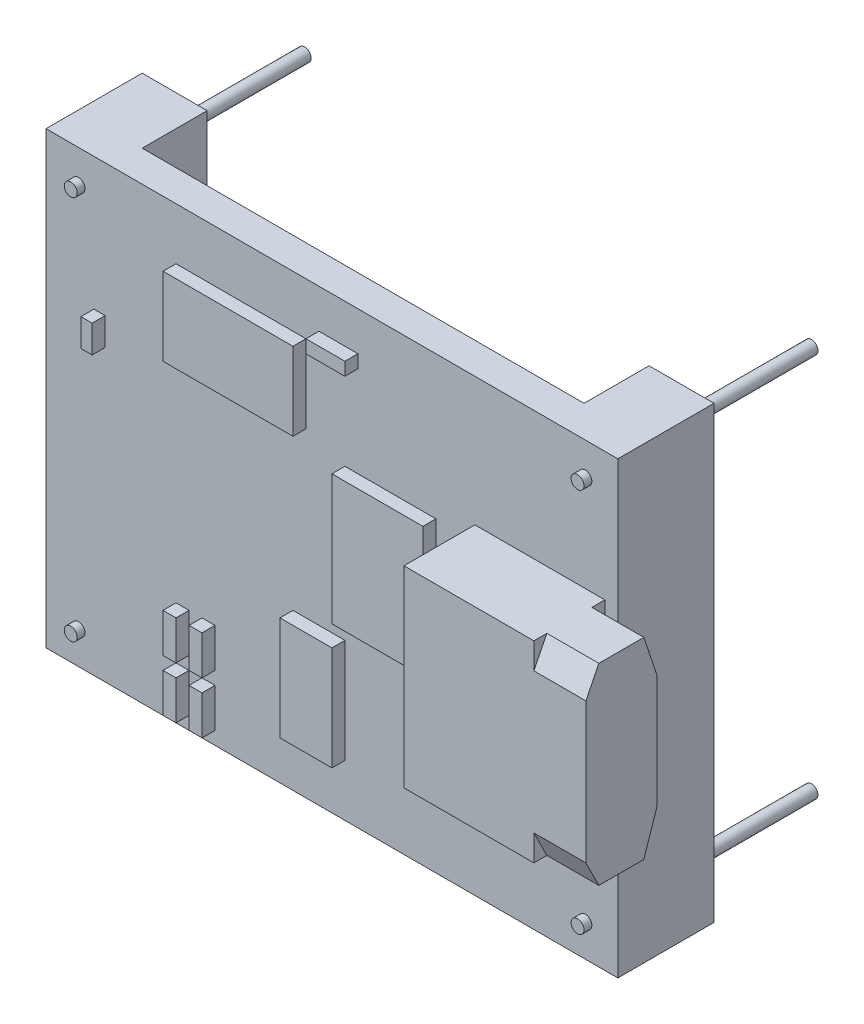
SolidWorks part; units mm, degrees
ref_plane "Plan de face" through (0, 0, 0) normal (0, 0, 1) x (1, 0, 0)
ref_plane "Plan de dessus" through (0, 0, 0) normal (0, 1, 0) x (1, 0, 0)
ref_plane "Plan de droite" through (0, 0, 0) normal (1, 0, 0) x (0, 0, -1)
sketch "Esquisse1" plane through (0, 0, 0) normal (0, 0, 1) x (1, 0, 0)
  line L1 (0, 0) -> (-22, 0)
  line L2 (0, 0) -> (0, 17.3)
  line L3 (0, 17.3) -> (-22, 17.3)
  line L4 (-22, 0) -> (-22, 17.3)
  dimension "D1" = 22
  dimension "D2" = 17.3
extrude "Boss.-Extru.1" add sketch "Esquisse1" along normal blind 1.2
sketch "Esquisse2" plane through (0, 0, 1.2) normal (0, 0, 1) x (1, 0, 0)
  line L0 (0, 0) -> (0, 17.3) construction
  line L1 (5.5, 4.95) -> (-5.5, 4.95)
  line L2 (5.5, 4.95) -> (5.5, 12.35)
  line L3 (5.5, 12.35) -> (-5.5, 12.35)
  line L4 (-5.5, 4.95) -> (-5.5, 12.35)
  line L5 (5.5, 4.95) -> (-5.5, 12.35) construction
  line L6 (5.5, 12.35) -> (-5.5, 4.95) construction
  line L7 (0, 12.35) -> (1.5, 12.35) construction
  line L8 (1.5, 12.35) -> (1.5, 4.95)
  point P0 (0, 8.65)
  line M5 (0, 0) -> (0, 17.3)
  dimension "D1" = 7.4
  dimension "D2" = 11
  dimension "D3" = 1.5
extrude "Boss.-Extru.2" add sketch "Esquisse2" along normal blind 2.73 contours L4 L1 L3 M5 | L8 L3 L1 M5 region at (0.75, 8.65, 1.2) region at (-2.75, 8.65, 1.2)
sketch "Esquisse3" plane through (0, 0, 0) normal (0, 0, -1) x (-1, 0, 0)
  line L0 (22, 0) -> (0, 0) construction
  line L1 (0, 17.3) -> (2.5, 17.3)
  line L2 (0, 17.3) -> (0, 0)
  line L3 (0, 0) -> (2.5, 0)
  line L4 (2.5, 17.3) -> (2.5, 0)
  line L5 (0, 17.3) -> (22, 17.3) construction
  line L6 (22, 0) -> (19.5, 0)
  line L7 (22, 0) -> (22, 17.3)
  line L8 (22, 17.3) -> (19.5, 17.3)
  line L9 (19.5, 0) -> (19.5, 17.3)
  dimension "D1" = 2.5
  dimension "D2" = 2.5
extrude "Boss.-Extru.3" add sketch "Esquisse3" along normal blind 2.5
sketch "Esquisse4" plane through (0, 0, -2.5) normal (0, 0, -1) x (-1, 0, 0)
  line L0 (2.5, 0) -> (2.5, 17.3) construction
  line L1 (0, 17.3) -> (2.5, 17.3)
  line L2 (0, 17.3) -> (0, 14.8)
  line L3 (0, 14.8) -> (2.5, 14.8)
  line L4 (2.5, 17.3) -> (2.5, 14.8)
  line L5 (2.5, 0) -> (2.5, 17.3) construction
  line L6 (0, 0) -> (2.5, 0)
  line L7 (0, 0) -> (0, 2.5)
  line L8 (0, 2.5) -> (2.5, 2.5)
  line L9 (2.5, 0) -> (2.5, 2.5)
  line L10 (22, 0) -> (22, 17.3) construction
  line L11 (19.5, 0) -> (22, 0)
  line L12 (19.5, 0) -> (19.5, 2.5)
  line L13 (19.5, 2.5) -> (22, 2.5)
  line L14 (22, 0) -> (22, 2.5)
  line L15 (19.5, 17.3) -> (19.5, 0) construction
  line L16 (22, 17.3) -> (19.5, 17.3)
  line L17 (22, 17.3) -> (22, 14.8)
  line L18 (22, 14.8) -> (19.5, 14.8)
  line L19 (19.5, 17.3) -> (19.5, 14.8)
  line L20 (0, 17.3) -> (2.5, 14.8) construction
  line L21 (19.5, 14.8) -> (22, 17.3) construction
  line L22 (22, 0) -> (19.5, 2.5) construction
  line L23 (2.5, 2.5) -> (0, 0) construction
  circle A0 centre (1.25, 1.25) radius 0.25
  circle A1 centre (1.25, 16.05) radius 0.25
  circle A2 centre (20.75, 16.05) radius 0.25
  circle A3 centre (20.75, 1.25) radius 0.25
  dimension "D5" = 0.5
  dimension "D6" = 0.5
  dimension "D7" = 0.5
  dimension "D8" = 0.5
  dimension "D1" = 2.5
  dimension "D2" = 2.5
  dimension "D3" = 2.5
  dimension "D4" = 2.5
extrude "Boss.-Extru.4" add sketch "Esquisse4" along normal blind 5 and the other way blind 4 contours A1 | A0 | A3 | A2
sketch "Esquisse5" plane through (0, 0, 1.2) normal (0, 0, 1) x (1, 0, 0)
  line L0 (-22, 0) -> (0, 0) construction
  line L1 (-10.5, 2) -> (-12.5, 2)
  line L2 (-10.5, 2) -> (-10.5, 6)
  line L3 (-10.5, 6) -> (-12.5, 6)
  line L4 (-12.5, 2) -> (-12.5, 6)
  line L5 (-15.5, 0.5) -> (-16, 0.5)
  line L6 (-15.5, 0.5) -> (-15.5, 2)
  line L7 (-15.5, 2) -> (-16, 2)
  line L8 (-16, 0.5) -> (-16, 2)
  line L9 (-16.5, 0.5) -> (-17, 0.5)
  line L10 (-16.5, 0.5) -> (-16.5, 2)
  line L11 (-16.5, 2) -> (-17, 2)
  line L12 (-17, 0.5) -> (-17, 2)
  line L13 (-15.5, 2.5) -> (-16, 2.5)
  line L14 (-15.5, 2.5) -> (-15.5, 4)
  line L15 (-15.5, 4) -> (-16, 4)
  line L16 (-16, 2.5) -> (-16, 4)
  line L17 (-16.5, 2.5) -> (-17, 2.5)
  line L18 (-16.5, 2.5) -> (-16.5, 4)
  line L19 (-16.5, 4) -> (-17, 4)
  line L20 (-17, 2.5) -> (-17, 4)
  line L21 (-12, 12.3) -> (-17, 12.3)
  line L22 (-12, 12.3) -> (-12, 15.3)
  line L23 (-12, 15.3) -> (-17, 15.3)
  line L24 (-17, 12.3) -> (-17, 15.3)
  line L25 (-10, 15.3) -> (-11.5, 15.3)
  line L26 (-10, 15.3) -> (-10, 15.8)
  line L27 (-10, 15.8) -> (-11.5, 15.8)
  line L28 (-11.5, 15.3) -> (-11.5, 15.8)
  line L33 (-19.7273, 11.1459) -> (-20.1614, 11.1459)
  line L34 (-19.7273, 11.1459) -> (-19.7273, 12.207)
  line L35 (-19.7273, 12.207) -> (-20.1614, 12.207)
  line L36 (-20.1614, 11.1459) -> (-20.1614, 12.207)
  line L37 (-22, 17.3) -> (-22, 0) construction
  line L38 (0, 17.3) -> (-22, 17.3) construction
  line L39 (-5.5, 4.95) -> (-5.5, 12.35) construction
  line L40 (-7, 6.8) -> (-10.5, 6.8)
  line L41 (-7, 6.8) -> (-7, 11.8)
  line L42 (-7, 11.8) -> (-10.5, 11.8)
  line L43 (-10.5, 6.8) -> (-10.5, 11.8)
  point P36 (-15.75, 2.5)
  point P37 (-16.75, 2.5)
  dimension "D1" = 2
  dimension "D2" = 4
  dimension "D3" = 1.5
  dimension "D4" = 1.5
  dimension "D5" = 1.5
  dimension "D6" = 1.5
  dimension "D7" = 0.5
  dimension "D8" = 0.5
  dimension "D9" = 0.5
  dimension "D10" = 0.5
  dimension "D11" = 0.5
  dimension "D12" = 0.5
  dimension "D13" = 0.5
  dimension "D14" = 0.5
  dimension "D15" = 0
  dimension "D16" = 0.5
  dimension "D17" = 5
  dimension "D18" = 3
  dimension "D19" = 2
  dimension "D20" = 5
  dimension "D21" = 3
  dimension "D22" = 2
  dimension "D23" = 5
  dimension "D26" = 1.5
  dimension "D27" = 0.5
  dimension "D28" = 1.5
  dimension "D29" = 12
  dimension "D31" = 3.5
  dimension "D32" = 5
  dimension "D33" = 1.5
  dimension "D34" = 5.5
extrude "Boss.-Extru.5" add sketch "Esquisse5" along normal blind 0.5
sketch "Esquisse8" plane through (1.5, 0, 0) normal (1, 0, 0) x (0, 0, -1)
  line L0 (-1.2, 4.95) -> (-1.2, 6.45) construction
  line L1 (-1.2, 4.95) -> (-1.2, 12.35) construction
  line L2 (-1.2, 6.45) -> (-1.2, 10.85) construction
  line L3 (-1.2, 12.35) -> (-1.2, 4.95) construction
  line L4 (-1.2, 10.85) -> (-1.2, 12.35) construction
  line L5 (-1.2, 6.45) -> (-1.2, 4.95)
  line L6 (-1.2, 4.95) -> (-1.7, 4.95)
  line L7 (-1.7, 2) -> (-1.7, 6) construction
  line L8 (-3.93, 4.95) -> (-1.2, 4.95) construction
  line L9 (-1.7, 4.95) -> (-1.2, 6.45)
  line L10 (-1.2, 10.85) -> (-1.7, 12.35)
  line L11 (-3.93, 12.35) -> (-1.2, 12.35) construction
  line L12 (-1.7, 12.3) -> (-1.7, 15.3) construction
  line L13 (-1.7, 12.35) -> (-1.2, 12.35)
  line L14 (-1.2, 12.35) -> (-1.2, 10.85)
  line L15 (-3.93, 4.95) -> (-3.93, 5.95) construction
  line L16 (-3.93, 12.35) -> (-3.93, 4.95) construction
  line L17 (-3.93, 5.95) -> (-3.93, 11.35) construction
  line L18 (-3.93, 11.35) -> (-3.93, 12.35) construction
  line L19 (-3.93, 12.35) -> (-3.43, 12.35) construction
  line L20 (-3.43, 12.35) -> (-3.43, 4.95) construction
  line L21 (-3.43, 4.95) -> (-3.93, 4.95) construction
  line L22 (-3.93, 4.95) -> (-3.93, 5.95)
  line L23 (-3.93, 5.95) -> (-3.43, 4.95)
  line L24 (-3.43, 4.95) -> (-3.93, 4.95)
  line L25 (-3.93, 11.35) -> (-3.43, 12.35)
  line L26 (-3.43, 12.35) -> (-3.93, 12.35)
  line L27 (-3.93, 12.35) -> (-3.93, 11.35)
  dimension "D1" = 1.5
  dimension "D2" = 1.5
  dimension "D3" = 1
  dimension "D4" = 0.5
  dimension "D5" = 1
extrude "Enlèv. mat.-Extru.4" cut sketch "Esquisse8" against normal blind 2
